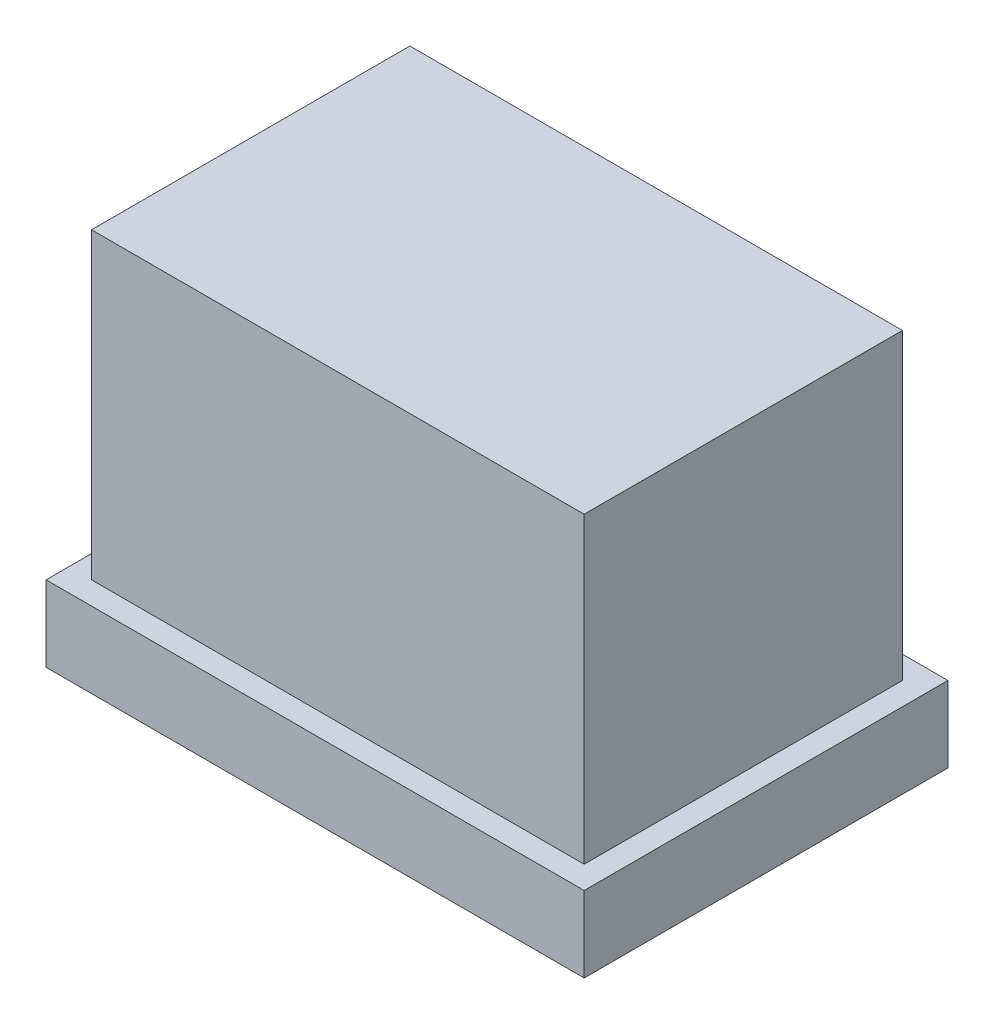
SolidWorks part; units mm, degrees
ref_plane "前视基准面" through (0, 0, 0) normal (0, 0, 1) x (1, 0, 0)
ref_plane "上视基准面" through (0, 0, 0) normal (0, 1, 0) x (1, 0, 0)
ref_plane "右视基准面" through (0, 0, 0) normal (1, 0, 0) x (0, 0, -1)
sketch "草图1" plane through (0, 0, 0) normal (0, 1, 0) x (1, 0, 0)
  line L0 (-0.6, -0.6) -> (-0.6, 9)
  line L1 (0, 0) -> (13, 0)
  line L2 (0, 0) -> (0, 8.4)
  line L3 (0, 8.4) -> (13, 8.4)
  line L4 (13, 0) -> (13, 8.4)
  line L5 (-0.6, 9) -> (13.6, 9)
  line L6 (13.6, -0.6) -> (13.6, 9)
  line L7 (-0.6, -0.6) -> (13.6, -0.6)
  dimension "D1" = 8.4
  dimension "D2" = 13
  dimension "D3" = 0.6
extrude "凸台-拉伸1" add sketch "草图1" along normal blind 8 contours L2 L1 L4 L3
extrude "凸台-拉伸2" add sketch "草图1<3>" against normal blind 2 separate body contours L1 L4 L3 L2 | L0 L7 L6 L5 L4 L1 L2 L3 region at (-0.4286, 0, -4.2) region at (6.5, 0, -4.2)
sketch "草图1<3>" plane through (0, 0, 0) normal (0, 1, 0) x (1, 0, 0) same geometry as "草图1"
